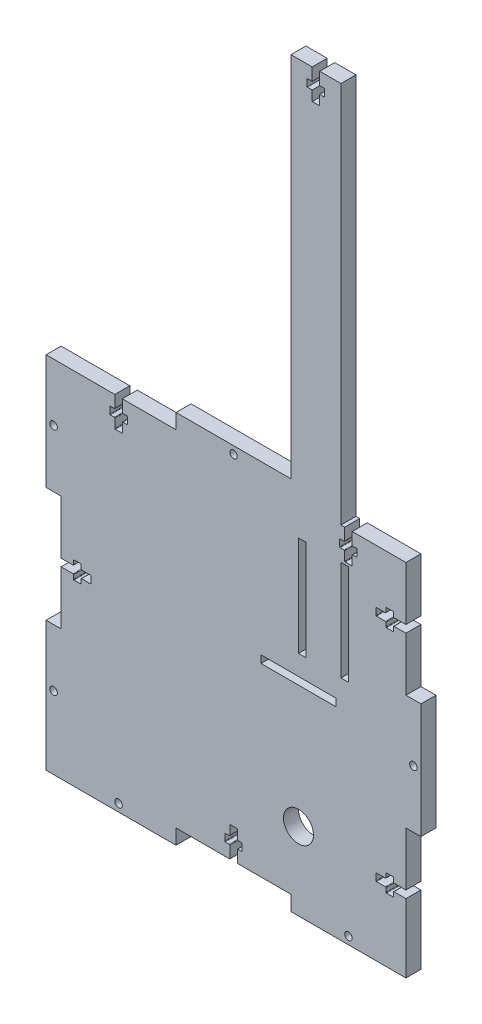
SolidWorks part; units mm, degrees
ref_plane "Front Plane" through (0, 0, 0) normal (0, 0, 1) x (1, 0, 0)
ref_plane "Top Plane" through (0, 0, 0) normal (0, 1, 0) x (1, 0, 0)
ref_plane "Right Plane" through (0, 0, 0) normal (1, 0, 0) x (0, 0, -1)
sketch "Sketch1" plane through (0, 0, 0) normal (0, 0, 1) x (1, 0, 0)
  line L0 (-69, 69) -> (-23, 69)
  line L5 (-75, -75) -> (75, -75) construction
  line L6 (-75, -75) -> (-75, 75) construction
  line L7 (-75, 75) -> (75, 75) construction
  line L8 (75, -75) -> (75, 75) construction
  line L9 (75, 23) -> (69, 23)
  line L10 (69, -23) -> (75, -23)
  line L11 (-69, -69) -> (69, -69) construction
  line L12 (-69, -69) -> (-69, 69) construction
  line L13 (-69, 69) -> (69, 69) construction
  line L14 (69, -69) -> (69, 69) construction
  line L15 (-69, -69) -> (69, 69) construction
  line L16 (69, -69) -> (69, -23)
  line L17 (-23, 69) -> (-23, 75)
  line L18 (-23, 75) -> (23, 75)
  line L19 (23, 75) -> (23, 69)
  line L20 (23, 69) -> (69, 69)
  line L21 (75, -23) -> (75, 23)
  line L22 (69, 23) -> (69, 69)
  line L23 (-75, 23) -> (-69, 23)
  line L24 (-69, 69) -> (-75, 69)
  line L25 (-75, 69) -> (-75, 23)
  line L26 (69, -69) -> (69, -75)
  line L27 (69, -75) -> (23, -75)
  line L28 (23, -75) -> (23, -69)
  line L29 (23, -69) -> (-23, -69)
  line L30 (-23, -69) -> (-23, -75)
  line L31 (-23, -75) -> (-69, -75)
  line L32 (-69, -75) -> (-69, -69) construction
  line L33 (-69, 23) -> (-69, -23)
  line L34 (-69, -23) -> (-75, -23)
  line L35 (-75, -23) -> (-75, -69)
  line L36 (-75, -69) -> (-69, -69) construction
  line L37 (-46, 69) -> (-46, -75) construction
  line L38 (-69, 69) -> (69, -69) construction
  line L39 (-75, -75) -> (-69, -75)
  line L40 (-75, -75) -> (-75, -69)
  point P0 (0, 0)
  point P6 (-7, -7)
  point P26 (0, -75)
  point P27 (-75, 0)
  dimension "D1" = 150
  dimension "D2" = 150
  dimension "D5" = 46
  dimension "D3" = 6
  dimension "D6" = 6
  dimension "D7" = 6
extrude "Box Side" add sketch "Sketch1" along normal blind 6
sketch "Sketch2" plane through (0, 0, 6) normal (0, 0, 1) x (1, 0, 0)
  line L0 (23, 72) -> (-23, 72) construction
  line L1 (23, 75) -> (23, 69) construction
  line L2 (-23, 69) -> (-23, 75) construction
  line L3 (-46, 69) -> (-46, -75) construction
  line L5 (0, 75) -> (0, 69) construction
  line L6 (-23, 75) -> (23, 75) construction
  line L7 (-69, 69) -> (69, 69) construction
  line L16 (-46, 69) -> (-46, -75) construction
  line L21 (0, -69) -> (0, 69) construction
  line L35 (-69, 69) -> (-23, 69) construction
  line L36 (-44.5, 69) -> (-44.5, 64.2)
  line L37 (-44.3, 64) -> (-42.7, 64)
  line L38 (-42.5, 63.8) -> (-42.5, 61.2)
  line L39 (-42.7, 61) -> (-44.3, 61)
  line L40 (-44.5, 60.8) -> (-44.5, 57.2)
  line L46 (-44.7, 57) -> (-47.3, 57)
  line L48 (-44.5, 69) -> (-47.5, 69)
  line L51 (-47.5, 60.8) -> (-47.5, 57.2)
  line L52 (-49.3, 61) -> (-47.7, 61)
  line L53 (-49.5, 63.8) -> (-49.5, 61.2)
  line L54 (-47.7, 64) -> (-49.3, 64)
  line L55 (-47.5, 69) -> (-47.5, 64.2)
  line L56 (47.5, 69) -> (47.5, 64.2)
  line L57 (47.7, 64) -> (49.3, 64)
  line L58 (49.5, 63.8) -> (49.5, 61.2)
  line L59 (49.3, 61) -> (47.7, 61)
  line L60 (47.5, 60.8) -> (47.5, 57.2)
  line L61 (44.5, 69) -> (47.5, 69)
  line L62 (44.7, 57) -> (47.3, 57)
  line L63 (44.5, 60.8) -> (44.5, 57.2)
  line L64 (42.7, 61) -> (44.3, 61)
  line L65 (42.5, 63.8) -> (42.5, 61.2)
  line L66 (44.3, 64) -> (42.7, 64)
  line L67 (44.5, 69) -> (44.5, 64.2)
  line L68 (-69, -69) -> (69, 69) construction
  line L69 (-69, -69) -> (69, 69) construction
  line L70 (75, 0) -> (69, 0) construction
  line L71 (72, 23) -> (72, -23) construction
  line L72 (69, 44.5) -> (64.2, 44.5)
  line L73 (64, 44.3) -> (64, 42.7)
  line L74 (63.8, 42.5) -> (61.2, 42.5)
  line L75 (61, 42.7) -> (61, 44.3)
  line L76 (60.8, 44.5) -> (57.2, 44.5)
  line L77 (57, 44.7) -> (57, 47.3)
  line L78 (69, 44.5) -> (69, 47.5)
  line L79 (60.8, 47.5) -> (57.2, 47.5)
  line L80 (61, 49.3) -> (61, 47.7)
  line L81 (63.8, 49.5) -> (61.2, 49.5)
  line L82 (64, 47.7) -> (64, 49.3)
  line L83 (69, 47.5) -> (64.2, 47.5)
  line L84 (69, -47.5) -> (64.2, -47.5)
  line L85 (64, -47.7) -> (64, -49.3)
  line L86 (63.8, -49.5) -> (61.2, -49.5)
  line L87 (61, -49.3) -> (61, -47.7)
  line L88 (60.8, -47.5) -> (57.2, -47.5)
  line L89 (69, -44.5) -> (69, -47.5)
  line L90 (57, -44.7) -> (57, -47.3)
  line L91 (60.8, -44.5) -> (57.2, -44.5)
  line L92 (61, -42.7) -> (61, -44.3)
  line L93 (63.8, -42.5) -> (61.2, -42.5)
  line L94 (64, -44.3) -> (64, -42.7)
  line L95 (69, -44.5) -> (64.2, -44.5)
  line L120 (-69, 69) -> (69, -69) construction
  line L121 (-69, 69) -> (69, -69) construction
  line L122 (-1.5, -69) -> (1.5, -69)
  line L123 (-23, -69) -> (23, -69) construction
  line L124 (1.5, -69) -> (1.5, -64.2)
  line L125 (1.7, -64) -> (3.3, -64)
  line L126 (3.5, -63.8) -> (3.5, -61.2)
  line L127 (3.3, -61) -> (1.7, -61)
  line L128 (1.5, -60.8) -> (1.5, -57.2)
  line L129 (1.3, -57) -> (-1.3, -57)
  line L130 (-1.5, -60.8) -> (-1.5, -57.2)
  line L131 (-3.3, -61) -> (-1.7, -61)
  line L132 (-3.5, -63.8) -> (-3.5, -61.2)
  line L133 (-1.7, -64) -> (-3.3, -64)
  line L134 (-1.5, -69) -> (-1.5, -64.2)
  line L135 (-69, -1.5) -> (-64.2, -1.5)
  line L136 (-64, -1.7) -> (-64, -3.3)
  line L137 (-63.8, -3.5) -> (-61.2, -3.5)
  line L138 (-61, -3.3) -> (-61, -1.7)
  line L139 (-60.8, -1.5) -> (-57.2, -1.5)
  line L140 (-57, 1.3) -> (-57, -1.3)
  line L141 (-60.8, 1.5) -> (-57.2, 1.5)
  line L142 (-61, 3.3) -> (-61, 1.7)
  line L143 (-63.8, 3.5) -> (-61.2, 3.5)
  line L144 (-64, 1.7) -> (-64, 3.3)
  line L145 (-69, 1.5) -> (-64.2, 1.5)
  line L146 (-69, -1.5) -> (-69, 1.5)
  line L147 (-69, -72) -> (-23, -72) construction
  line L148 (-23, 69) -> (-75, 69) construction
  line L149 (-23, -75) -> (-23, -69) construction
  line L150 (-69, -69) -> (-69, -75) construction
  line L151 (-75, -75) -> (-23, -75) construction
  circle A0 centre (0, 72) radius 1.5
  arc A1 (-44.5, 57.2) -> (-44.7, 57) centre (-44.7, 57.2) cw
  arc A2 (-44.3, 61) -> (-44.5, 60.8) centre (-44.3, 60.8) ccw
  arc A3 (-42.5, 61.2) -> (-42.7, 61) centre (-42.7, 61.2) cw
  arc A4 (-42.7, 64) -> (-42.5, 63.8) centre (-42.7, 63.8) cw
  arc A5 (-44.5, 64.2) -> (-44.3, 64) centre (-44.3, 64.2) ccw
  arc A6 (-47.5, 64.2) -> (-47.7, 64) centre (-47.7, 64.2) cw
  arc A7 (-49.3, 64) -> (-49.5, 63.8) centre (-49.3, 63.8) ccw
  arc A8 (-49.5, 61.2) -> (-49.3, 61) centre (-49.3, 61.2) ccw
  arc A9 (-47.7, 61) -> (-47.5, 60.8) centre (-47.7, 60.8) cw
  arc A10 (-47.5, 57.2) -> (-47.3, 57) centre (-47.3, 57.2) ccw
  arc A11 (47.5, 57.2) -> (47.3, 57) centre (47.3, 57.2) cw
  arc A12 (47.7, 61) -> (47.5, 60.8) centre (47.7, 60.8) ccw
  arc A13 (49.5, 61.2) -> (49.3, 61) centre (49.3, 61.2) cw
  arc A14 (49.3, 64) -> (49.5, 63.8) centre (49.3, 63.8) cw
  arc A15 (47.5, 64.2) -> (47.7, 64) centre (47.7, 64.2) ccw
  arc A16 (44.5, 64.2) -> (44.3, 64) centre (44.3, 64.2) cw
  arc A17 (42.7, 64) -> (42.5, 63.8) centre (42.7, 63.8) ccw
  arc A18 (42.5, 61.2) -> (42.7, 61) centre (42.7, 61.2) ccw
  arc A19 (44.3, 61) -> (44.5, 60.8) centre (44.3, 60.8) cw
  arc A20 (44.5, 57.2) -> (44.7, 57) centre (44.7, 57.2) ccw
  arc A21 (57.2, 44.5) -> (57, 44.7) centre (57.2, 44.7) cw
  arc A22 (61, 44.3) -> (60.8, 44.5) centre (60.8, 44.3) ccw
  arc A23 (61.2, 42.5) -> (61, 42.7) centre (61.2, 42.7) cw
  arc A24 (64, 42.7) -> (63.8, 42.5) centre (63.8, 42.7) cw
  arc A25 (64.2, 44.5) -> (64, 44.3) centre (64.2, 44.3) ccw
  arc A26 (64.2, 47.5) -> (64, 47.7) centre (64.2, 47.7) cw
  arc A27 (64, 49.3) -> (63.8, 49.5) centre (63.8, 49.3) ccw
  arc A28 (61.2, 49.5) -> (61, 49.3) centre (61.2, 49.3) ccw
  arc A29 (61, 47.7) -> (60.8, 47.5) centre (60.8, 47.7) cw
  arc A30 (57.2, 47.5) -> (57, 47.3) centre (57.2, 47.3) ccw
  arc A31 (57.2, -47.5) -> (57, -47.3) centre (57.2, -47.3) cw
  arc A32 (61, -47.7) -> (60.8, -47.5) centre (60.8, -47.7) ccw
  arc A33 (61.2, -49.5) -> (61, -49.3) centre (61.2, -49.3) cw
  arc A34 (64, -49.3) -> (63.8, -49.5) centre (63.8, -49.3) cw
  arc A35 (64.2, -47.5) -> (64, -47.7) centre (64.2, -47.7) ccw
  arc A36 (64.2, -44.5) -> (64, -44.3) centre (64.2, -44.3) cw
  arc A37 (64, -42.7) -> (63.8, -42.5) centre (63.8, -42.7) ccw
  arc A38 (61.2, -42.5) -> (61, -42.7) centre (61.2, -42.7) ccw
  arc A39 (61, -44.3) -> (60.8, -44.5) centre (60.8, -44.3) cw
  arc A40 (57.2, -44.5) -> (57, -44.7) centre (57.2, -44.7) ccw
  circle A41 centre (72, 0) radius 1.5
  arc A62 (1.5, -57.2) -> (1.3, -57) centre (1.3, -57.2) ccw
  arc A63 (1.7, -61) -> (1.5, -60.8) centre (1.7, -60.8) cw
  arc A64 (3.5, -61.2) -> (3.3, -61) centre (3.3, -61.2) ccw
  arc A65 (3.3, -64) -> (3.5, -63.8) centre (3.3, -63.8) ccw
  arc A66 (1.5, -64.2) -> (1.7, -64) centre (1.7, -64.2) cw
  arc A67 (-1.5, -64.2) -> (-1.7, -64) centre (-1.7, -64.2) ccw
  arc A68 (-3.3, -64) -> (-3.5, -63.8) centre (-3.3, -63.8) cw
  arc A69 (-3.5, -61.2) -> (-3.3, -61) centre (-3.3, -61.2) cw
  arc A70 (-1.7, -61) -> (-1.5, -60.8) centre (-1.7, -60.8) ccw
  arc A71 (-1.5, -57.2) -> (-1.3, -57) centre (-1.3, -57.2) cw
  arc A72 (-57.2, -1.5) -> (-57, -1.3) centre (-57.2, -1.3) ccw
  arc A73 (-61, -1.7) -> (-60.8, -1.5) centre (-60.8, -1.7) cw
  arc A74 (-61.2, -3.5) -> (-61, -3.3) centre (-61.2, -3.3) ccw
  arc A75 (-64, -3.3) -> (-63.8, -3.5) centre (-63.8, -3.3) ccw
  arc A76 (-64.2, -1.5) -> (-64, -1.7) centre (-64.2, -1.7) cw
  arc A77 (-64.2, 1.5) -> (-64, 1.7) centre (-64.2, 1.7) ccw
  arc A78 (-64, 3.3) -> (-63.8, 3.5) centre (-63.8, 3.3) cw
  arc A79 (-61.2, 3.5) -> (-61, 3.3) centre (-61.2, 3.3) cw
  arc A80 (-61, 1.7) -> (-60.8, 1.5) centre (-60.8, 1.7) ccw
  arc A81 (-57.2, 1.5) -> (-57, 1.3) centre (-57.2, 1.3) cw
  circle A82 centre (-46, -72) radius 1.5
  circle A83 centre (46, -72) radius 1.5
  circle A84 centre (-72, 46) radius 1.5
  circle A85 centre (-72, -46) radius 1.5
  point P6 (0, 72)
  point P38 (0, 0)
  point P56 (-46, 57)
  point P88 (46, 57)
  point P161 (57, 46)
  point P162 (57, -46)
  point P198 (0, -57)
  point P231 (-57, 0)
  point P234 (-42.5, 62.5)
  dimension "D1" = 3
  dimension "D2" = 0.2
  dimension "D8" = 0.2
  dimension "D14" = 3
  dimension "D4" = 3
  dimension "D7" = 1.5
  dimension "D10" = 3
  dimension "D12" = 1.5
  dimension "D9" = 12
  dimension "D11" = 5
  dimension "D13" = 7
  dimension "D3" = 12
  dimension "D5" = 7
  dimension "D6" = 5
extrude "Screw Cut-outs" cut sketch "Sketch2" against normal through all
sketch "Bearing Hole" plane through (0, 0, 6) normal (0, 0, 1) x (1, 0, 0)
  line L0 (20, -69) -> (50020, -69) construction
  line L1 (69, -44.5) -> (69, -23) construction
  line L4 (26, -41) -> (50026, -41) construction
  line L5 (26.5774, -47) -> (50026.5774, -47) construction
  line L8 (29, -52) -> (29, -50052) construction
  circle A0 centre (26, -44) radius 3 construction
  circle A1 centre (26, -54) radius 15 construction
  circle A2 centre (26, -44) radius 6
  dimension "D2" = 6
  dimension "D4" = 30
  dimension "D5" = 12
  dimension "D1" = 7
  dimension "D3" = 43
extrude "Shaft Hole" cut sketch "Bearing Hole" against normal through all
sketch "Sketch4" plane through (0, 0, 0) normal (0, 0, -1) x (-1, 0, 0)
  line L0 (-72, 1.5) -> (49928, 1.5) construction
  line L1 (-41, 8) -> (-11, 8)
  line L2 (-41, 8) -> (-41, 5)
  line L3 (-41, 5) -> (-11, 5)
  line L4 (-11, 8) -> (-11, 5)
  line L5 (-75, -23) -> (-75, 23) construction
  line L6 (-69, 23) -> (-69, 44.5) construction
  line L7 (-46, 56) -> (-43, 56)
  line L8 (-46, 56) -> (-46, 16)
  line L9 (-46, 16) -> (-43, 16)
  line L10 (-43, 56) -> (-43, 16)
  line L11 (-29, 56) -> (-26, 56)
  line L12 (-29, 56) -> (-29, 16)
  line L13 (-29, 16) -> (-26, 16)
  line L14 (-26, 56) -> (-26, 16)
  line L15 (-44.5, 69) -> (-23, 69) construction
  circle A1 centre (-72, 0) radius 1.5 construction
  point P18 (-29, 36)
  dimension "D1" = 3.5
  dimension "D2" = 30
  dimension "D3" = 3
  dimension "D4" = 34
  dimension "D5" = 14
  dimension "D6" = 23
  dimension "D7" = 13
  dimension "D8" = 3
  dimension "D9" = 40
extrude "Grooves" cut sketch "Sketch4" against normal up to surface (6 mm away) up to face at (32, -44, 6)
sketch "Sketch5" plane through (0, 69, 0) normal (0, 1, 0) x (1, 0, 0)
  line L0 (69, 0) -> (47.5, 0) construction
  line L1 (23, -6) -> (43, -6)
  line L2 (23, -6) -> (23, 0)
  line L3 (23, 0) -> (43, 0)
  line L4 (43, -6) -> (43, 0)
  line L5 (75, -6) -> (75, 0) construction
  dimension "D1" = 32
extrude "Boss-Extrude1" add sketch "Sketch5" along normal blind 153
sketch "Sketch6" plane through (0, 0, 0) normal (0, 0, -1) x (-1, 0, 0)
  line L0 (-34.5, 222) -> (-34.5, 217)
  line L1 (-43, 222) -> (-23, 222) construction
  line L2 (-34.5, 217) -> (-36.5, 217)
  line L3 (-36.5, 217) -> (-36.5, 214)
  line L4 (-36.5, 214) -> (-34.5, 214)
  line L5 (-34.5, 214) -> (-34.5, 210)
  line L6 (-34.5, 210) -> (-31.5, 210)
  line L7 (-31.5, 210) -> (-31.5, 214)
  line L8 (-31.5, 214) -> (-29.5, 214)
  line L9 (-29.5, 214) -> (-29.5, 217)
  line L10 (-29.5, 217) -> (-31.5, 217)
  line L11 (-31.5, 217) -> (-31.5, 222)
  line L12 (-34.5, 222) -> (-31.5, 222)
  line L13 (-29.5, 214) -> (-36.5, 214)
  point P4 (-33, 210)
  point P16 (-33, 222)
  point P17 (-33, 214)
  point P18 (-33, 222)
  dimension "D1" = 3
  dimension "D2" = 7
  dimension "D3" = 5
  dimension "D4" = 12
  dimension "D5" = 3
extrude "Cut-Extrude1" cut sketch "Sketch6" against normal through all contours L13 L8 L9 L10 L11 L12 L0 L2 L3 L4 | L7 L13 L5 L6 region at (33, 217.1667, 0) region at (33, 212, 0)
equation "\"filletRadius\"=0.2"
equation "\"D8@Sketch2\"=\"filletRadius\""
equation "\"D2@Sketch2\"=\"filletRadius\""
equation "\"fingerWidth\"= 46"
equation "\"D5@Sketch1\"=\"fingerWidth\""
equation "\"wallThickness\"= 6"
equation "\"D3@Sketch1\" = \"wallThickness\""
equation "\"D6@Sketch1\" = \"wallThickness\""
equation "\"D7@Sketch1\" = \"wallThickness\""
equation "\"D1@Box Side\" = \"wallThickness\""
equation "\"M3\"= 3"
equation "\"D14@Sketch2\"=\"M3\""
equation "\"D1@Sketch2\"=\"M3\""
equation "\"D12@Sketch2\"=\"M3\"/2"
equation "\"nutThickness\"=3"
equation "\"D10@Sketch2\" = \"nutThickness\""
equation "\"boltLength\"= 12"
equation "\"D9@Sketch2\" = \"boltLength\""
equation "\"distanceToNut\"= 5"
equation "\"D11@Sketch2\" = \"distanceToNut\""
equation "\"D13@Sketch2\" = \"nutWidth\""
equation "\"D7@Sketch2\"=\"M3\"/2"
equation "\"D4@Sketch2\" = \"nutThickness\""
equation "\"D3@Sketch2\" = \"boltLength\""
equation "\"D5@Sketch2\" = \"nutWidth\""
equation "\"D6@Sketch2\" = \"distanceToNut\""
equation "\"sideLength\"=150"
equation "\"D1@Sketch1\"=\"sideLength\""
equation "\"D2@Sketch1\"=\"sideLength\""
equation "\"nutWidth\"=7"
equation "\"D1@Sketch6\"=\"M3\""
equation "\"D2@Sketch6\"=\"nutWidth\""
equation "\"D3@Sketch6\"=\"distanceToNut\""
equation "\"D4@Sketch6\"=\"boltLength\""
equation "\"D5@Sketch6\"=\"nutThickness\""
